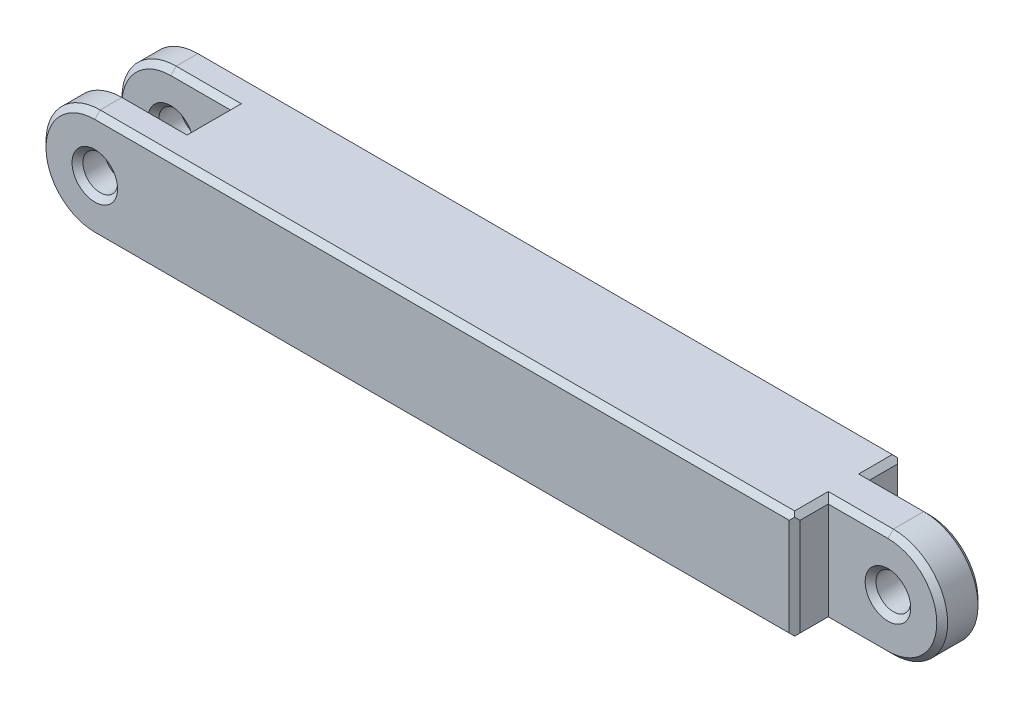
SolidWorks part; units mm, degrees
ref_plane "Front" through (0, 0, 0) normal (0, 0, 1) x (1, 0, 0)
ref_plane "Top" through (0, 0, 0) normal (0, 1, 0) x (1, 0, 0)
ref_plane "Right" through (0, 0, 0) normal (1, 0, 0) x (0, 0, -1)
sketch "Sketch1" plane through (0, 0, 0) normal (0, 0, 1) x (1, 0, 0)
  line L0 (0, 5) -> (70, 5)
  line L2 (70, -5) -> (0, -5)
  circle A0 centre (0, 0) radius 5 construction
  arc A2 (0, 5) -> (0, -5) centre (0, 0) ccw
  circle A3 centre (0, 0) radius 1.6
  circle A4 centre (70, 0) radius 5 construction
  circle A5 centre (70, 0) radius 1.6
  arc A6 (70, 5) -> (70, -5) centre (70, 0) cw
extrude "Boss-Extrude1" add sketch "Sketch1" along normal blind 10
sketch "Sketch2" plane through (0, 0, 10) normal (0, 0, 1) x (1, 0, 0)
  line L0 (5.5, 5) -> (5.5, -5)
  line L1 (70, 5) -> (0, 5) construction
  line L2 (0, -5) -> (70, -5) construction
  line L3 (5.5, -5) -> (0, -5)
  line L4 (0, 5) -> (5.5, 5)
  line L5 (35, 15.4001) -> (35, -9.7362) construction
  circle A0 centre (0, 0) radius 5 construction
  arc A1 (0, -5) -> (0, 5) centre (0, 0) cw
  dimension "D1" = 5.5
  dimension "D2" = 35
extrude "Cut-Extrude1" cut sketch "Sketch2" against normal blind 4 from offset 3 offset against normal yes
chamfer "Chamfer1" distance 0.5 angle 45 22 edges at (71.6, 0, 0) (1.6, 0, 0) (35, -5, 0) (75, 0, 0) (35, 5, 0) (-5, 0, 0) (71.6, 0, 10) (35, 5, 10) (75, 0, 10) (35, -5, 10) (-5, 0, 10) (1.6, 0, 10) (5.5, -5, 5) (-1.6, 0, 3) (-1.6, 0, 7) (2.75, 5, 3) (2.75, -5, 3) (-5, 0, 3) (2.75, -5, 7) (-5, 0, 7) (5.5, 5, 5) (2.75, 5, 7)
sketch "Sketch3" plane through (0, 0, 10) normal (0, 0, 1) x (1, 0, 0)
  line L0 (64.5, 5) -> (64.5, -5)
  line L1 (0, 5) -> (70, 5) construction
  line L2 (70, -5) -> (0, -5) construction
  line L3 (64.5, 5) -> (70, 5)
  line L4 (70, -5) -> (64.5, -5)
  arc A1 (70, 5) -> (70, -5) centre (70, 0) cw
extrude "Cut-Extrude2" cut sketch "Sketch3" against normal blind 3.1
sketch "Sketch4" plane through (0, 0, 6.9) normal (0, 0, 1) x (1, 0, 0)
  line L0 (64.5, 5) -> (64.5, -5)
  line L1 (64.5, -5) -> (70, -5)
  line L2 (64.5, -5) -> (70, -5) construction
  line L3 (70, 5) -> (64.5, 5)
  arc A0 (70, -5) -> (70, 5) centre (70, 0) ccw construction
  arc A1 (70, -5) -> (70, 5) centre (70, 0) ccw
extrude "Cut-Extrude3" cut sketch "Sketch4" against normal blind 3.1 from offset 3.8 offset against normal yes
chamfer "Chamfer2" distance 0.5 angle 45 14 edges at (68.4, 0, 6.9) (71.6, 0, 3.1) (64.5, -5, 1.8) (64.5, 0, 0) (67.25, -5, 3.1) (75, 0, 3.1) (67.25, 5, 3.1) (64.5, 5, 1.8) (64.5, -5, 8.2) (64.5, 0, 10) (67.25, -5, 6.9) (75, 0, 6.9) (64.5, 5, 8.2) (67.25, 5, 6.9)
